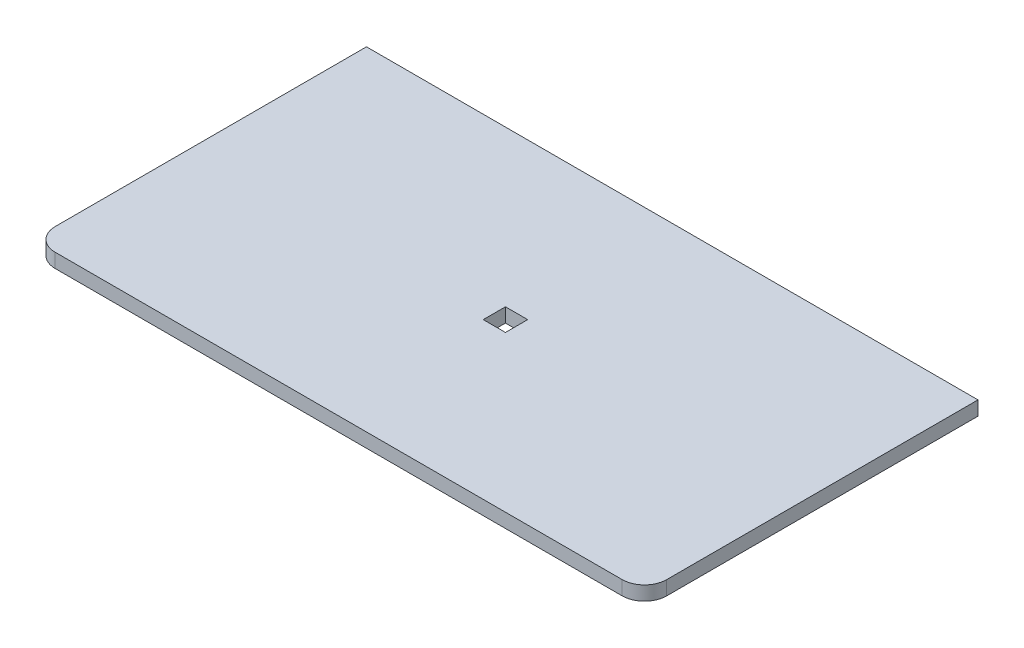
SolidWorks part; units mm, degrees
ref_plane "Front Plane" through (0, 0, 0) normal (0, 0, 1) x (1, 0, 0)
ref_plane "Top Plane" through (0, 0, 0) normal (0, 1, 0) x (1, 0, 0)
ref_plane "Right Plane" through (0, 0, 0) normal (1, 0, 0) x (0, 0, -1)
sketch "Sketch2" plane through (0, 0, 0) normal (0, 1, 0) x (1, 0, 0)
  line L1 (-137.5, 75) -> (137.5, 75)
  line L2 (-137.5, 75) -> (-137.5, -75)
  line L3 (-137.5, -75) -> (137.5, -75)
  line L4 (137.5, 75) -> (137.5, -75)
  line L5 (-137.5, 75) -> (137.5, -75) construction
  line L6 (-137.5, -75) -> (137.5, 75) construction
  point P0 (0, 0)
  dimension "D1" = 275
  dimension "D2" = 150
extrude "Boss-Extrude1" add sketch "Sketch2" along normal blind 6.35
fillet "Fillet1" radius 10 2 edges at (137.5, 3.175, 75) (-137.5, 3.175, 75)
sketch "Sketch3" plane through (0, 6.35, 0) normal (0, 1, 0) x (1, 0, 0)
  line L1 (-5, 5) -> (5, 5)
  line L2 (-5, 5) -> (-5, -5)
  line L3 (-5, -5) -> (5, -5)
  line L4 (5, 5) -> (5, -5)
  line L5 (-5, 5) -> (5, -5) construction
  line L6 (-5, -5) -> (5, 5) construction
  point P0 (0, 0)
  dimension "D1" = 10
  dimension "D2" = 10
extrude "Cut-Extrude1" cut sketch "Sketch3" against normal through all
equation "\"D2@Sketch2\"=150"
